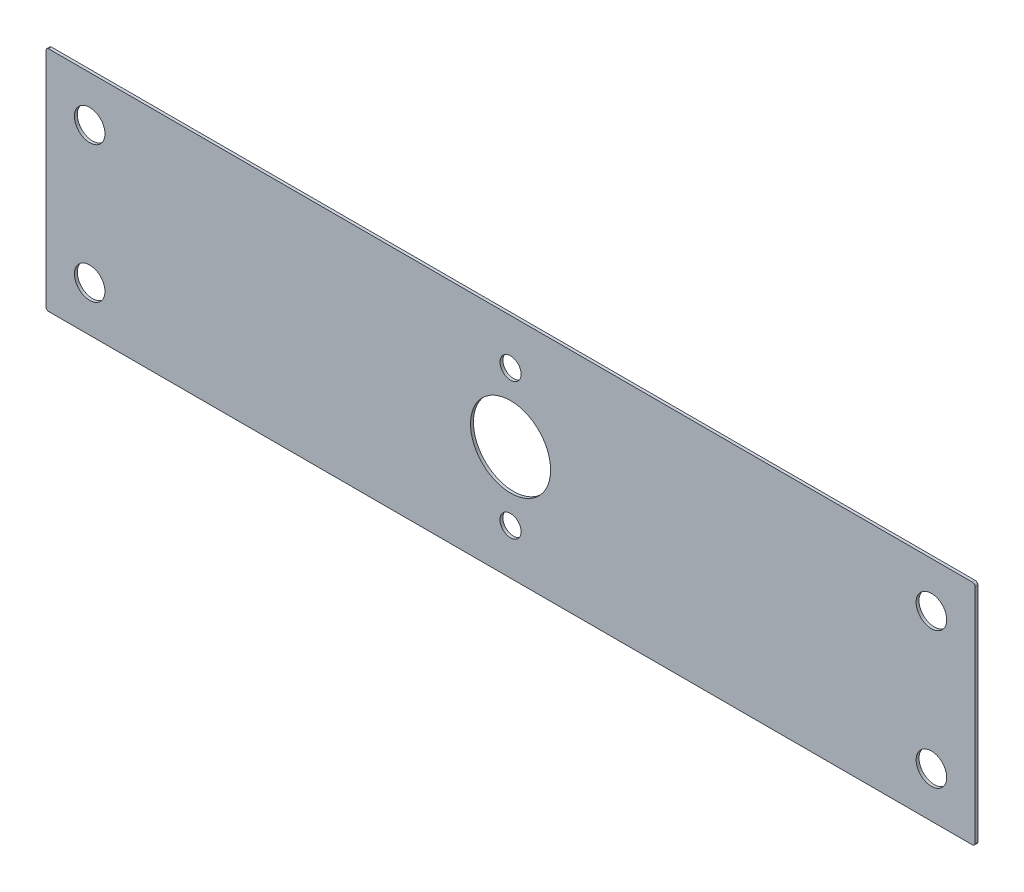
SolidWorks part; units mm, degrees
material "ASTM A36 Steel"
ref_plane "Front Plane" through (0, 0, 0) normal (0, 0, 1) x (1, 0, 0)
ref_plane "Top Plane" through (0, 0, 0) normal (0, 1, 0) x (1, 0, 0)
ref_plane "Right Plane" through (0, 0, 0) normal (1, 0, 0) x (0, 0, -1)
ref_axis "Axis1" through (0, 0, 14.936) along (0, 0, -1)
sketch "Sketch1" plane through (0, 0, 0) normal (0, 0, 1) x (1, 0, 0)
  line L1 (-64.8208, 15.875) -> (64.8208, 15.875)
  line L2 (-64.8208, 15.875) -> (-64.8208, -15.875)
  line L3 (-64.8208, -15.875) -> (64.8208, -15.875)
  line L4 (64.8208, 15.875) -> (64.8208, -15.875)
  circle A0 centre (58.7248, 9.525) radius 2.1336
  circle A1 centre (58.7248, -9.525) radius 2.1336
  circle A2 centre (0, 0) radius 5.588
  circle A3 centre (0, 9.525) radius 1.4732
  circle A4 centre (0, -9.525) radius 1.4732
  circle A5 centre (-58.7248, 9.525) radius 2.1336
  circle A6 centre (-58.7248, -9.525) radius 2.1336
  point P4 (64.8208, 0)
  point P5 (0, 15.875)
  dimension "D3" = 11.176
  dimension "D4" = 2.9464
  dimension "D5" = 9.525
  dimension "D6" = 9.525
  dimension "D7" = 58.7248
  dimension "D10" = 9.525
  dimension "D11" = 6.096
  dimension "D12" = 4.2672
  dimension "D13" = 6.096
  dimension "D1" = 31.75
  dimension "D2" = 129.6416
  dimension "D8" = 58.7248
  dimension "D9" = 9.525
extrude "Boss-Extrude1" add sketch "Sketch1" along normal blind 0.4064
fillet "Fillet1" radius 0.381 4 edges at (-64.8208, 15.875, 0.2032) (-64.8208, -15.875, 0.2032) (64.8208, -15.875, 0.2032) (64.8208, 15.875, 0.2032)
